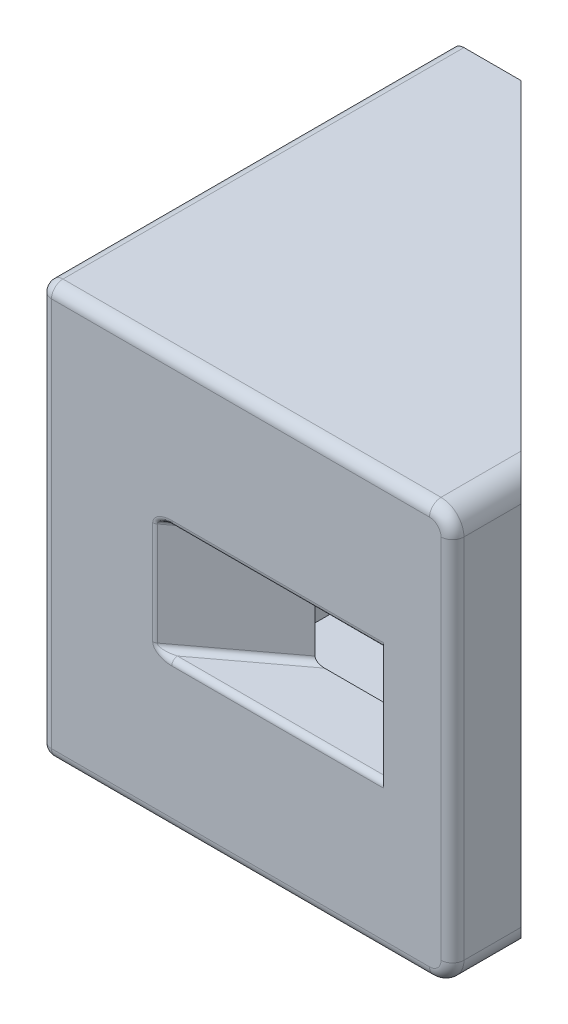
SolidWorks part; units mm, degrees
ref_plane "Front Plane" through (0, 0, 0) normal (0, 0, 1) x (1, 0, 0)
ref_plane "Top Plane" through (0, 0, 0) normal (0, 1, 0) x (1, 0, 0)
ref_plane "Right Plane" through (0, 0, 0) normal (1, 0, 0) x (0, 0, -1)
sketch "Sketch1" plane through (0, 0, 0) normal (0, 1, 0) x (1, 0, 0)
  line L0 (0, 0) -> (0, 18)
  line L1 (0, 18) -> (3, 18)
  line L2 (3, 18) -> (18, 3)
  line L3 (18, 3) -> (18, 0)
  line L4 (18, 0) -> (0, 0)
  dimension "D1" = 18
  dimension "D2" = 18
  dimension "D3" = 3
  dimension "D5" = 90
extrude "Boss-Extrude1" add sketch "Sketch1" along normal blind 18
sketch "Sketch2" plane through (0, 0, -18) normal (0, 0, -1) x (-1, 0, 0)
  line L0 (-18, 18) -> (-3, 18) construction
  line L1 (-3, 16) -> (-18, 16)
  line L2 (-3, 16) -> (-3, 2)
  line L3 (-3, 2) -> (-18, 2)
  line L4 (-18, 16) -> (-18, 2)
  line L5 (-18, 0) -> (-3, 0) construction
  line L7 (-3, 18) -> (-3, 0) construction
  line L8 (-18, 18) -> (-18, 0) construction
  dimension "D1" = 2
  dimension "D2" = 2
  dimension "D3" = 0
  dimension "D4" = 0
extrude "Cut-Extrude1" cut sketch "Sketch2" against normal up to vertex (15 mm away) up to point (18, 0, -3)
sketch "Sketch3" plane through (0, 0, -3) normal (0, 0, -1) x (-1, 0, 0)
  line L1 (-15, 11.5) -> (-9, 11.5)
  line L2 (-15, 11.5) -> (-15, 6.5)
  line L3 (-15, 6.5) -> (-9, 6.5)
  line L4 (-9, 11.5) -> (-9, 6.5)
  line L5 (-18, 16) -> (-18, 2) construction
  point P6 (-18, 9)
  point P7 (-15, 9)
  point P8 (0, 0)
  dimension "D1" = 6
  dimension "D2" = 5
  dimension "D3" = 3
sketch "Sketch4" plane through (0, 0, 0) normal (0, 0, 1) x (1, 0, 0)
  line L1 (15, 11.5) -> (5, 11.5)
  line L2 (15, 11.5) -> (15, 6.5)
  line L3 (15, 6.5) -> (5, 6.5)
  line L4 (5, 11.5) -> (5, 6.5)
  dimension "D1" = 10
loft "Cut-Loft2" cut profiles "Sketch3", "Sketch4"
sketch "Sketch5" plane through (3, 0, 0) normal (1, 0, 0) x (0, 0, -1)
  line L0 (18, 2) -> (18, 16) construction
  line L1 (9, 11.5) -> (15, 11.5)
  line L2 (9, 11.5) -> (9, 6.5)
  line L3 (9, 6.5) -> (15, 6.5)
  line L4 (15, 11.5) -> (15, 6.5)
  point P6 (18, 9)
  point P7 (15, 9)
  dimension "D1" = 6
  dimension "D2" = 5
  dimension "D3" = 3
sketch "Sketch6" plane through (0, 0, 0) normal (-1, 0, 0) x (0, 0, 1)
  line L1 (-15, 11.5) -> (-5, 11.5)
  line L2 (-15, 11.5) -> (-15, 6.5)
  line L3 (-15, 6.5) -> (-5, 6.5)
  line L4 (-5, 11.5) -> (-5, 6.5)
  dimension "D1" = 10
loft "Cut-Loft3" cut profiles "Sketch5", "Sketch6"
fillet "Fillet8" radius 1 2 edges at (18, 0, -1.5) (18, 18, -1.5)
fillet "Fillet9" radius 0.5 5 edges at (8.5, 18, 0) (17.7071, 17.7071, 0) (8.5, 0, 0) (17.7071, 0.2929, 0) (18, 9, 0)
fillet "Fillet10" radius 0.5 5 edges at (0, 0, -9.25) (0, 0.1464, -0.1464) (0, 9, 0) (0, 17.8536, -0.1464) (0, 18, -9.25)
fillet "Fillet11" radius 0.25 5 edges
fillet "Fillet12" radius 0.25 5 edges
